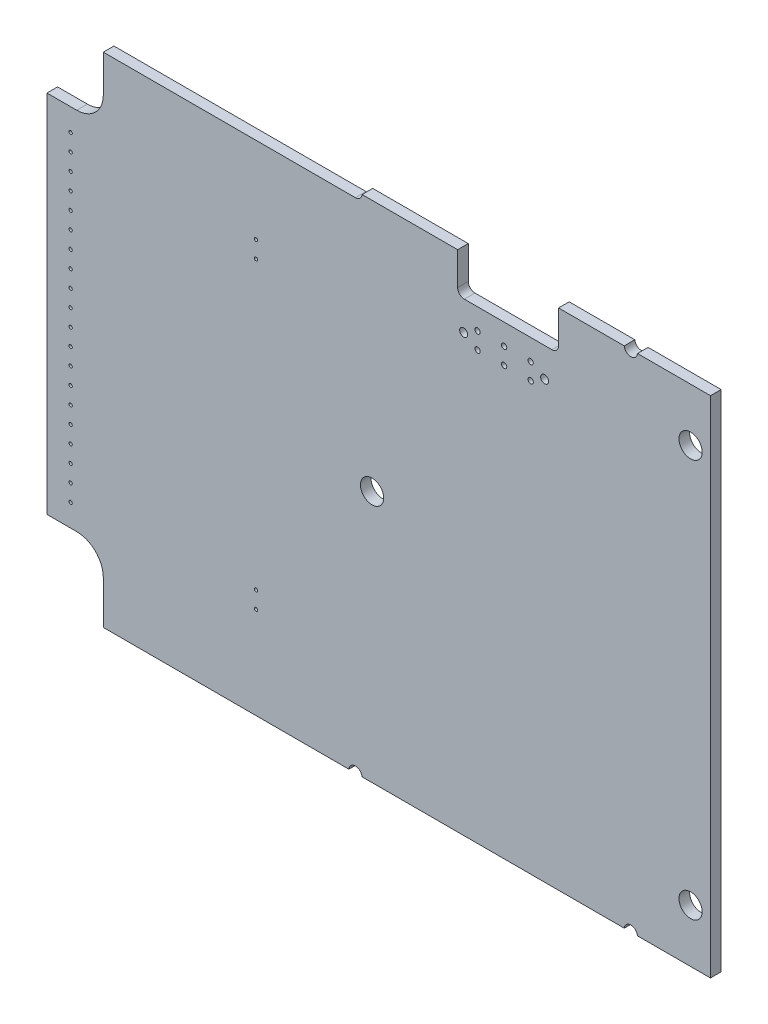
SolidWorks part; units mm, degrees
ref_plane "Płaszczyzna przednia" through (0, 0, 0) normal (0, 0, 1) x (1, 0, 0)
ref_plane "Płaszczyzna górna" through (0, 0, 0) normal (0, 1, 0) x (1, 0, 0)
ref_plane "Płaszczyzna prawa" through (0, 0, 0) normal (1, 0, 0) x (0, 0, -1)
sketch "Sketch1" plane through (0, 0, 0) normal (0, 0, 1) x (1, 0, 0)
  line L0 (293.2004, -11.8195) -> (291.7004, -11.8195) construction
  line L1 (291.7004, -11.8195) -> (291.7004, -12.7695) construction
  line L2 (308.8504, 57.7305) -> (322.0504, 57.7305)
  line L3 (293.2004, -12.7695) -> (293.2004, -11.8195) construction
  line L4 (334.7004, -11.8195) -> (333.2004, -11.8195) construction
  line L5 (333.2004, -11.8195) -> (333.2004, -12.7695) construction
  line L6 (333.2004, 63.6805) -> (333.2004, 63.2305) construction
  line L7 (334.7004, -12.7695) -> (334.7004, -11.8195) construction
  line L8 (376.2004, -11.8195) -> (374.7004, -11.8195) construction
  line L9 (374.7004, -11.8195) -> (374.7004, -12.7695) construction
  line L10 (333.2004, 63.2305) -> (333.2004, 63.1805) construction
  line L11 (376.2004, -12.7695) -> (376.2004, -11.8195) construction
  line L12 (393.4504, -5.0695) -> (393.4504, -6.5695) construction
  line L13 (393.4504, -6.5695) -> (394.4004, -6.5695) construction
  line L14 (333.2004, 63.6805) -> (332.9539, 63.6805) construction
  line L15 (394.4004, -5.0695) -> (393.4504, -5.0695) construction
  line L16 (393.4504, 57.9305) -> (393.4504, 56.4305) construction
  line L17 (393.4504, 56.4305) -> (394.4004, 56.4305) construction
  line L18 (333.2004, 63.6805) -> (323.0504, 63.6805) construction
  line L19 (394.4004, 57.9305) -> (393.4504, 57.9305) construction
  line L20 (333.2004, 63.1805) -> (334.7004, 63.1805) construction
  line L21 (334.7004, 63.1805) -> (334.7004, 64.1305) construction
  line L22 (333.2004, 64.425) -> (333.2004, 63.6805) construction
  line L23 (333.2004, 64.1305) -> (333.2004, 63.1805) construction
  line L24 (374.7004, 63.1805) -> (376.2004, 63.1805) construction
  line L25 (376.2004, 63.1805) -> (376.2004, 64.1305) construction
  line L26 (334.7004, 63.6805) -> (334.7004, 64.425) construction
  line L27 (374.7004, 64.1305) -> (374.7004, 63.1805) construction
  line L28 (291.7004, 63.1805) -> (293.2004, 63.1805) construction
  line L29 (293.2004, 63.1805) -> (293.2004, 64.1305) construction
  line L30 (291.4539, 63.6805) -> (254.4504, 63.6805) construction
  line L31 (291.7004, 64.1305) -> (291.7004, 63.1805) construction
  line L32 (376.2004, -13.3195) -> (390.9504, -13.3195) construction
  line L33 (394.9504, -9.3195) -> (394.9504, -6.5695) construction
  line L34 (394.9504, -5.0695) -> (394.9504, 56.4305) construction
  line L35 (394.9504, 57.9305) -> (394.9504, 60.6805) construction
  line L36 (390.9504, 64.6805) -> (376.2004, 64.6805) construction
  line L37 (374.7004, 64.6805) -> (334.7004, 64.6805) construction
  line L38 (307.8504, 64.6805) -> (307.8504, 65.8305) construction
  line L39 (323.0504, 64.6805) -> (323.0504, 65.8305) construction
  line L40 (333.2004, 64.6805) -> (323.0504, 64.6805) construction
  line L41 (307.8504, 64.6805) -> (293.2004, 64.6805) construction
  line L42 (291.7004, 64.6805) -> (246.9504, 64.6805) construction
  line L43 (246.9504, -8.4262) -> (246.9504, 59.7871) construction
  line L44 (334.7004, -13.3195) -> (374.7004, -13.3195) construction
  line L45 (293.2004, -13.3195) -> (333.2004, -13.3195) construction
  line L46 (246.9504, -13.3195) -> (291.7004, -13.3195) construction
  line L47 (293.2004, -11.8195) -> (291.7004, -11.8195) construction
  line L48 (291.7004, -11.8195) -> (291.7004, -13.3195) construction
  line L50 (293.2004, -13.3195) -> (293.2004, -11.8195) construction
  line L51 (334.7004, -11.8195) -> (333.2004, -11.8195) construction
  line L52 (333.2004, -11.8195) -> (333.2004, -13.3195) construction
  line L54 (334.7004, -13.3195) -> (334.7004, -11.8195) construction
  line L55 (376.2004, -11.8195) -> (374.7004, -11.8195) construction
  line L56 (374.7004, -11.8195) -> (374.7004, -13.3195) construction
  line L58 (376.2004, -13.3195) -> (376.2004, -13.0641) construction
  line L59 (393.4504, -5.0695) -> (393.4504, -6.5695) construction
  line L60 (393.4504, -6.5695) -> (394.9504, -6.5695) construction
  line L62 (394.9504, -5.0695) -> (393.4504, -5.0695) construction
  line L63 (393.4504, 57.9305) -> (393.4504, 56.4305) construction
  line L64 (393.4504, 56.4305) -> (394.6949, 56.4305) construction
  line L66 (394.9504, 57.9305) -> (393.4504, 57.9305) construction
  line L67 (333.2004, 63.1805) -> (334.7004, 63.1805) construction
  line L68 (334.7004, 63.1805) -> (334.7004, 63.6805) construction
  line L70 (333.2004, 64.6805) -> (333.2004, 64.425) construction
  line L71 (374.7004, 63.1805) -> (376.2004, 63.1805) construction
  line L72 (376.2004, 63.1805) -> (376.2004, 63.6805) construction
  line L74 (374.7004, 64.425) -> (374.7004, 63.1805) construction
  line L75 (291.7004, 63.1805) -> (293.2004, 63.1805) construction
  line L76 (293.2004, 63.1805) -> (293.2004, 64.6805) construction
  line L78 (291.7004, 64.425) -> (291.7004, 63.6805) construction
  line L79 (376.2004, -13.3195) -> (390.9504, -13.3195) construction
  line L80 (394.9504, -9.3195) -> (394.9504, -6.5695) construction
  line L81 (394.9504, -5.0695) -> (394.9504, 56.4305) construction
  line L82 (394.9504, 57.9305) -> (394.9504, 60.6805) construction
  line L83 (390.9504, 64.6805) -> (376.2004, 64.6805) construction
  line L84 (374.7004, 64.6805) -> (334.7004, 64.6805) construction
  line L85 (307.8504, 64.6805) -> (307.8504, 65.8305) construction
  line L86 (323.0504, 58.7305) -> (323.0504, 63.6805)
  line L87 (333.2004, 64.6805) -> (323.0504, 64.6805) construction
  line L88 (307.8504, 64.6805) -> (293.2004, 64.6805) construction
  line L89 (291.7004, 64.6805) -> (246.9504, 64.6805) construction
  line L90 (246.9504, -13.3195) -> (246.9504, -3.883) construction
  line L91 (334.7004, -13.3195) -> (374.7004, -13.3195) construction
  line L92 (293.2004, -13.3195) -> (333.2004, -13.3195) construction
  line L93 (246.9504, -13.3195) -> (291.7004, -13.3195) construction
  line L94 (247.9504, -12.3195) -> (247.9504, -8.942) construction
  line L95 (254.4504, -12.3195) -> (291.4539, -12.3195)
  line L96 (293.4469, -12.3195) -> (332.9539, -12.3195)
  line L97 (334.9469, -12.3195) -> (374.4539, -12.3195)
  line L98 (376.4469, -12.3195) -> (390.9504, -12.3195)
  line L99 (393.9504, -9.3195) -> (393.9504, -6.8161)
  line L100 (393.9504, -4.823) -> (393.9504, 56.4305)
  line L101 (393.9504, 58.177) -> (393.9504, 60.6805)
  line L102 (317.8504, 58.7305) -> (317.8504, 63.2305)
  line L103 (317.8504, 63.2305) -> (307.8504, 63.2305)
  line L104 (307.8504, 63.2305) -> (307.8504, 58.7305)
  line L105 (307.8504, 58.7305) -> (311.3504, 58.7305)
  line L106 (311.3504, 58.7305) -> (311.3504, 62.7305)
  line L107 (311.3504, 62.7305) -> (314.3504, 62.7305)
  line L108 (314.3504, 62.7305) -> (314.3504, 58.7305)
  line L109 (314.3504, 58.7305) -> (317.8504, 58.7305)
  line L112 (307.8504, 63.6805) -> (307.8504, 58.7305)
  line L113 (307.8504, 58.7305) -> (311.3504, 58.7305) construction
  line L114 (311.3504, 58.7305) -> (311.3504, 62.7305) construction
  line L115 (311.3504, 62.7305) -> (314.3504, 62.7305) construction
  line L116 (314.3504, 62.7305) -> (314.3504, 58.7305) construction
  line L117 (314.3504, 58.7305) -> (323.0504, 58.7305) construction
  line L118 (390.9504, 63.6805) -> (376.4469, 63.6805)
  line L119 (374.4539, 63.6805) -> (334.9469, 63.6805)
  line L120 (307.8504, 63.6805) -> (293.4469, 63.6805)
  line L121 (332.9539, 63.6805) -> (323.0504, 63.6805)
  line L122 (307.8504, 64.6805) -> (307.8504, 63.6805) construction
  line L123 (323.0504, 64.6805) -> (323.0504, 65.8305) construction
  line L124 (323.0504, 63.6805) -> (323.0504, 64.6805) construction
  line L125 (334.7004, 64.425) -> (334.7004, 64.6805) construction
  line L126 (334.9469, 63.6805) -> (334.7004, 63.6805) construction
  line L127 (374.7004, 63.6805) -> (334.7004, 63.6805) construction
  line L128 (291.7004, 63.6805) -> (291.4539, 63.6805) construction
  line L129 (291.7004, 63.6805) -> (247.9504, 63.6805) construction
  line L130 (291.7004, 64.6805) -> (291.7004, 64.425) construction
  line L131 (293.4469, 63.6805) -> (293.2004, 63.6805) construction
  line L132 (307.8504, 63.6805) -> (293.2004, 63.6805) construction
  line L133 (374.7004, 63.6805) -> (374.4539, 63.6805) construction
  line L134 (374.7004, 64.6805) -> (374.7004, 64.425) construction
  line L135 (376.2004, 63.6805) -> (376.2004, 64.425) construction
  line L136 (376.2004, 64.425) -> (376.2004, 64.6805) construction
  line L137 (376.4469, 63.6805) -> (376.2004, 63.6805) construction
  line L138 (390.9504, 63.6805) -> (376.2004, 63.6805) construction
  line L139 (394.6949, 56.4305) -> (394.9504, 56.4305) construction
  line L140 (393.9504, 57.9305) -> (393.9504, 58.177) construction
  line L141 (393.9504, 57.9305) -> (393.9504, 60.6805) construction
  line L142 (393.9504, -5.0695) -> (393.9504, -4.823) construction
  line L143 (393.9504, -5.0695) -> (393.9504, 56.4305) construction
  line L144 (393.9504, -6.8161) -> (393.9504, -6.5695) construction
  line L145 (393.9504, -9.3195) -> (393.9504, -6.5695) construction
  line L146 (376.2004, -13.0641) -> (376.2004, -12.3195) construction
  line L147 (376.2004, -12.3195) -> (376.2004, -11.8195) construction
  line L148 (376.2004, -12.3195) -> (376.4469, -12.3195) construction
  line L149 (376.2004, -12.3195) -> (390.9504, -12.3195) construction
  line L150 (293.2004, -12.3195) -> (293.4469, -12.3195) construction
  line L151 (332.9539, -12.3195) -> (333.2004, -12.3195) construction
  line L152 (293.2004, -12.3195) -> (333.2004, -12.3195) construction
  line L153 (334.7004, -12.3195) -> (334.9469, -12.3195) construction
  line L154 (334.7004, -12.3195) -> (374.7004, -12.3195) construction
  line L155 (254.4504, 57.1805) -> (254.4504, 62.7636)
  line L156 (291.4539, -12.3195) -> (291.7004, -12.3195) construction
  line L157 (247.9504, -12.3195) -> (291.7004, -12.3195) construction
  line L158 (250.4504, 53.1805) -> (245.9504, 53.1805)
  line L159 (254.4504, -5.8195) -> (254.4504, -12.3195)
  line L160 (250.4504, -1.8195) -> (245.9504, -1.8195)
  line L161 (247.9504, -1.8195) -> (247.9504, 53.1805) construction
  line L162 (247.9504, -4.1612) -> (247.9504, -2.697) construction
  line L163 (247.9504, -2.697) -> (247.9504, -1.8195) construction
  line L164 (247.9504, -12.3195) -> (247.9504, 63.6805) construction
  line L165 (247.9504, -8.942) -> (247.9504, -7.4778) construction
  line L166 (247.9504, -7.4778) -> (247.9504, -4.1612) construction
  line L167 (247.9504, -12.3195) -> (254.4504, -12.3195) construction
  line L168 (247.9504, 60.303) -> (247.9504, 63.6805) construction
  line L169 (254.4504, 63.6805) -> (247.9504, 63.6805) construction
  line L170 (247.9504, 58.8388) -> (247.9504, 60.303) construction
  line L171 (246.9504, 59.117) -> (246.9504, 64.6805) construction
  line L172 (246.9504, -13.3195) -> (246.9504, 64.6805) construction
  line L173 (246.9504, 55.244) -> (246.9504, 59.117) construction
  line L174 (247.9504, 55.5222) -> (247.9504, 58.8388) construction
  line L175 (246.9504, -3.883) -> (246.9504, 55.244) construction
  line L176 (247.9504, 54.058) -> (247.9504, 55.5222) construction
  line L177 (247.9504, 53.1805) -> (247.9504, 54.058) construction
  line L178 (249.5254, 49.8105) -> (277.4654, 49.8105) construction
  line L179 (249.5254, 49.8105) -> (249.5254, 47.2705) construction
  line L180 (374.4539, -12.3195) -> (374.7004, -12.3195) construction
  line L181 (245.4504, -8.8119) -> (245.4504, 59.8484) construction
  line L182 (245.4504, -8.8119) -> (245.4504, 59.8484) construction
  line L183 (245.9504, -1.8195) -> (245.9504, 53.1805)
  line L184 (245.9504, -8.8119) -> (245.9504, -1.8195) construction
  line L185 (245.9504, 53.1805) -> (245.9504, 59.8484) construction
  line L186 (245.9504, -8.8119) -> (245.9504, 59.8484) construction
  line L187 (292.4504, 62.7636) -> (254.4504, 62.7636)
  line L188 (254.4504, 62.7636) -> (254.4504, 63.6805) construction
  line L189 (291.7004, 63.6805) -> (291.7004, 63.2305) construction
  line L190 (291.7004, 63.2305) -> (291.7004, 63.1805) construction
  circle A0 centre (250.4504, -5.8195) radius 1.2 construction
  arc A1 (390.9504, -13.3195) -> (394.9504, -9.3195) centre (390.9504, -9.3195) ccw construction
  arc A2 (394.9504, 60.6805) -> (390.9504, 64.6805) centre (390.9504, 60.6805) ccw construction
  circle A3 centre (249.5254, 49.8105) radius 0.25 construction
  circle A4 centre (250.4504, 57.1805) radius 3 construction
  circle A5 centre (250.4504, 57.1805) radius 1.2 construction
  circle A6 centre (250.4504, -5.8195) radius 3 construction
  circle A7 centre (342.9504, -4.3195) radius 2.5 construction
  circle A8 centre (342.9504, -4.3195) radius 1 construction
  circle A9 centre (375.4504, -5.8195) radius 3 construction
  circle A10 centre (375.4504, -5.8195) radius 1.2 construction
  circle A11 centre (375.4504, 57.1805) radius 3 construction
  circle A12 centre (375.4504, 57.1805) radius 1.2 construction
  circle A13 centre (342.9504, 55.6805) radius 2.5 construction
  circle A14 centre (342.9504, 55.6805) radius 1 construction
  circle A15 centre (294.9504, 25.6805) radius 2.5 construction
  circle A16 centre (294.9504, 25.6805) radius 1 construction
  circle A17 centre (250.4504, -5.8195) radius 1.2 construction
  arc A18 (390.9504, -13.3195) -> (394.9504, -9.3195) centre (390.9504, -9.3195) ccw construction
  arc A19 (394.9504, 60.6805) -> (390.9504, 64.6805) centre (390.9504, 60.6805) ccw construction
  circle A20 centre (249.5254, 49.8105) radius 0.25 construction
  arc A21 (247.9504, 55.5222) -> (247.9504, 58.8388) centre (250.4504, 57.1805) ccw construction
  circle A22 centre (250.4504, 57.1805) radius 1.2 construction
  circle A23 centre (250.4504, -5.8195) radius 3 construction
  circle A24 centre (342.9504, -4.3195) radius 2.5 construction
  circle A25 centre (342.9504, -4.3195) radius 1 construction
  circle A26 centre (375.4504, -5.8195) radius 3 construction
  circle A27 centre (375.4504, -5.8195) radius 1.2 construction
  circle A28 centre (375.4504, 57.1805) radius 3 construction
  circle A29 centre (375.4504, 57.1805) radius 1.2 construction
  circle A30 centre (342.9504, 55.6805) radius 2.5 construction
  circle A31 centre (342.9504, 55.6805) radius 1 construction
  circle A32 centre (294.9504, 25.6805) radius 2.5 construction
  circle A33 centre (294.9504, 25.6805) radius 1 construction
  circle A34 centre (294.9504, 25.6805) radius 1.75
  circle A35 centre (342.9504, 55.6805) radius 1.75
  circle A36 centre (342.9504, -4.3195) radius 1.75
  arc A37 (250.4504, 53.1805) -> (254.4504, 57.1805) centre (250.4504, 57.1805) ccw
  arc A38 (254.4504, -5.8195) -> (250.4504, -1.8195) centre (250.4504, -5.8195) ccw
  circle A39 centre (375.4504, -5.8195) radius 4
  circle A40 centre (375.4504, 57.1805) radius 4
  arc A41 (390.9504, -12.3195) -> (393.9504, -9.3195) centre (390.9504, -9.3195) ccw
  arc A42 (393.9504, 60.6805) -> (390.9504, 63.6805) centre (390.9504, 60.6805) ccw
  arc A43 (307.8504, 58.7305) -> (308.8504, 57.7305) centre (308.8504, 58.7305) ccw
  arc A44 (322.0504, 57.7305) -> (323.0504, 58.7305) centre (322.0504, 58.7305) ccw
  circle A46 centre (333.2004, 63.1805) radius 0.05 construction
  circle A47 centre (334.7004, 63.1805) radius 0.05 construction
  arc A48 (332.9539, 63.6805) -> (334.9469, 63.6805) centre (333.9504, 63.7636) ccw
  arc A49 (333.2004, 64.425) -> (332.9539, 63.6805) centre (333.9504, 63.7636) ccw construction
  arc A50 (334.9469, 63.6805) -> (334.7004, 64.425) centre (333.9504, 63.7636) ccw construction
  arc A51 (334.7004, 64.425) -> (333.2004, 64.425) centre (333.9504, 63.7636) ccw construction
  circle A52 centre (291.7004, 63.1805) radius 0.05 construction
  circle A53 centre (293.2004, 63.1805) radius 0.05 construction
  arc A54 (293.2399, 63.1498) -> (293.4469, 63.6805) centre (292.4504, 63.7636) ccw
  arc A55 (291.7004, 64.425) -> (291.4539, 63.6805) centre (292.4504, 63.7636) ccw construction
  arc A56 (293.2004, 64.425) -> (291.7004, 64.425) centre (292.4504, 63.7636) ccw construction
  arc A57 (293.4469, 63.6805) -> (293.2004, 64.425) centre (292.4504, 63.7636) ccw construction
  circle A58 centre (374.7004, 63.1805) radius 0.05 construction
  circle A59 centre (376.2004, 63.1805) radius 0.05 construction
  arc A60 (374.4539, 63.6805) -> (376.4469, 63.6805) centre (375.4504, 63.7636) ccw
  arc A61 (374.7004, 64.425) -> (374.4539, 63.6805) centre (375.4504, 63.7636) ccw construction
  arc A62 (376.2004, 64.425) -> (374.7004, 64.425) centre (375.4504, 63.7636) ccw construction
  arc A63 (376.4469, 63.6805) -> (376.2004, 64.425) centre (375.4504, 63.7636) ccw construction
  circle A64 centre (393.4504, 57.9305) radius 0.05 construction
  circle A65 centre (393.4504, 56.4305) radius 0.05 construction
  arc A66 (393.9504, 58.177) -> (393.9504, 56.1839) centre (394.0335, 57.1805) ccw
  arc A67 (394.6949, 56.4305) -> (394.6949, 57.9305) centre (394.0335, 57.1805) ccw construction
  arc A68 (393.9504, 56.1839) -> (394.6949, 56.4305) centre (394.0335, 57.1805) ccw construction
  arc A69 (394.6949, 57.9305) -> (393.9504, 58.177) centre (394.0335, 57.1805) ccw construction
  circle A70 centre (393.4504, -6.5695) radius 0.05 construction
  circle A71 centre (393.4504, -5.0695) radius 0.05 construction
  arc A72 (393.9504, -4.823) -> (393.9504, -6.8161) centre (394.0335, -5.8195) ccw
  arc A73 (394.9504, -5.4204) -> (393.9504, -4.823) centre (394.0335, -5.8195) ccw construction
  arc A74 (393.9504, -6.8161) -> (394.9504, -6.2186) centre (394.0335, -5.8195) ccw construction
  arc A75 (394.9504, -6.2186) -> (394.9504, -5.4204) centre (394.0335, -5.8195) ccw construction
  circle A76 centre (374.7004, -11.8195) radius 0.05 construction
  circle A77 centre (376.2004, -11.8195) radius 0.05 construction
  circle A78 centre (333.2004, -11.8195) radius 0.05 construction
  circle A79 centre (334.7004, -11.8195) radius 0.05 construction
  circle A80 centre (291.7004, -11.8195) radius 0.05 construction
  circle A81 centre (293.2004, -11.8195) radius 0.05 construction
  arc A82 (376.4469, -12.3195) -> (374.4539, -12.3195) centre (375.4504, -12.4026) ccw
  arc A83 (334.9469, -12.3195) -> (332.9539, -12.3195) centre (333.9504, -12.4026) ccw
  arc A84 (293.4469, -12.3195) -> (291.4539, -12.3195) centre (292.4504, -12.4026) ccw
  arc A85 (374.4539, -12.3195) -> (374.7004, -13.0641) centre (375.4504, -12.4026) ccw construction
  arc A86 (374.7004, -13.0641) -> (376.2004, -13.0641) centre (375.4504, -12.4026) ccw construction
  arc A87 (376.2004, -13.0641) -> (376.4469, -12.3195) centre (375.4504, -12.4026) ccw construction
  arc A88 (332.9539, -12.3195) -> (333.2004, -13.0641) centre (333.9504, -12.4026) ccw construction
  arc A89 (333.2004, -13.0641) -> (334.7004, -13.0641) centre (333.9504, -12.4026) ccw construction
  arc A90 (334.7004, -13.0641) -> (334.9469, -12.3195) centre (333.9504, -12.4026) ccw construction
  arc A91 (293.2004, -13.0641) -> (293.4469, -12.3195) centre (292.4504, -12.4026) ccw construction
  arc A92 (291.7004, -13.0641) -> (293.2004, -13.0641) centre (292.4504, -12.4026) ccw construction
  arc A93 (291.4539, -12.3195) -> (291.7004, -13.0641) centre (292.4504, -12.4026) ccw construction
  arc A94 (247.9504, -2.697) -> (246.9504, -3.883) centre (250.4504, -5.8195) ccw construction
  arc A95 (250.4504, -1.8195) -> (247.9504, -2.697) centre (250.4504, -5.8195) ccw construction
  circle A96 centre (250.4504, -5.8195) radius 4 construction
  arc A97 (246.9504, -3.883) -> (246.9504, -7.756) centre (250.4504, -5.8195) ccw construction
  arc A98 (246.9504, -7.756) -> (247.9504, -8.942) centre (250.4504, -5.8195) ccw construction
  arc A99 (247.9504, -8.942) -> (254.4504, -5.8195) centre (250.4504, -5.8195) ccw construction
  arc A100 (247.9504, 60.303) -> (246.9504, 59.117) centre (250.4504, 57.1805) ccw construction
  circle A101 centre (250.4504, 57.1805) radius 4 construction
  arc A102 (246.9504, 59.117) -> (246.9504, 55.244) centre (250.4504, 57.1805) ccw construction
  arc A103 (247.9504, 58.8388) -> (247.9504, 55.5222) centre (250.4504, 57.1805) ccw construction
  circle A104 centre (250.4504, 57.1805) radius 3 construction
  arc A105 (246.9504, 55.244) -> (247.9504, 54.058) centre (250.4504, 57.1805) ccw construction
  arc A106 (247.9504, 54.058) -> (250.4504, 53.1805) centre (250.4504, 57.1805) ccw construction
  arc A107 (254.4504, 57.1805) -> (247.9504, 60.303) centre (250.4504, 57.1805) ccw construction
  circle A108 centre (277.4654, 49.8105) radius 0.25 construction
  circle A109 centre (277.4654, 47.2705) radius 0.25 construction
  arc A110 (291.4539, 63.6805) -> (291.6609, 63.1498) centre (292.4504, 63.7636) ccw construction
  arc A111 (292.4504, 62.7636) -> (293.2399, 63.1498) centre (292.4504, 63.7636) ccw
  arc A112 (291.6609, 63.1498) -> (292.4504, 62.7636) centre (292.4504, 63.7636) ccw construction
  circle A126 centre (277.4654, 4.0905) radius 0.25 construction
  circle A127 centre (277.4654, 1.5505) radius 0.25 construction
  circle A128 centre (249.5254, 47.2705) radius 0.25 construction
  circle A129 centre (249.5254, 44.7305) radius 0.25 construction
  circle A130 centre (249.5254, 42.1905) radius 0.25 construction
  circle A131 centre (249.5254, 39.6505) radius 0.25 construction
  circle A132 centre (249.5254, 37.1105) radius 0.25 construction
  circle A133 centre (249.5254, 34.5705) radius 0.25 construction
  circle A134 centre (249.5254, 32.0305) radius 0.25 construction
  circle A135 centre (249.5254, 29.4905) radius 0.25 construction
  circle A136 centre (249.5254, 26.9505) radius 0.25 construction
  circle A137 centre (249.5254, 24.4105) radius 0.25 construction
  circle A138 centre (249.5254, 21.8705) radius 0.25 construction
  circle A139 centre (249.5254, 19.3305) radius 0.25 construction
  circle A140 centre (249.5254, 16.7905) radius 0.25 construction
  circle A141 centre (249.5254, 14.2505) radius 0.25 construction
  circle A142 centre (249.5254, 11.7105) radius 0.25 construction
  circle A143 centre (249.5254, 9.1705) radius 0.25 construction
  circle A144 centre (249.5254, 6.6305) radius 0.25 construction
  circle A145 centre (249.5254, 4.0905) radius 0.25 construction
  circle A146 centre (249.5254, 1.5505) radius 0.25 construction
  circle A147 centre (277.4654, 44.7305) radius 0.25 construction
  circle A148 centre (277.4654, 42.1905) radius 0.25 construction
  circle A149 centre (277.4654, 39.6505) radius 0.25 construction
  circle A150 centre (277.4654, 37.1105) radius 0.25 construction
  circle A151 centre (277.4654, 34.5705) radius 0.25 construction
  circle A152 centre (277.4654, 32.0305) radius 0.25 construction
  circle A153 centre (277.4654, 29.4905) radius 0.25 construction
  circle A154 centre (277.4654, 26.9505) radius 0.25 construction
  circle A155 centre (277.4654, 24.4105) radius 0.25 construction
  circle A156 centre (277.4654, 21.8705) radius 0.25 construction
  circle A157 centre (277.4654, 19.3305) radius 0.25 construction
  circle A158 centre (277.4654, 16.7905) radius 0.25 construction
  circle A159 centre (277.4654, 14.2505) radius 0.25 construction
  circle A160 centre (277.4654, 11.7105) radius 0.25 construction
  circle A161 centre (277.4654, 9.1705) radius 0.25 construction
  circle A162 centre (277.4654, 6.6305) radius 0.25 construction
  point P225 (254.4504, -5.8195)
  dimension "D5" = 1
  dimension "D6" = 0.1
  dimension "D7" = 2
  dimension "D10" = 27.94
  dimension "D11" = 2.54
  dimension "D1" = 0
  dimension "D2" = 0.75
  dimension "D3" = 1
  dimension "D4" = 1
  dimension "D12" = 0.5
  dimension "D8" = 2
  dimension "D9" = 20
sketch "Sketch3" plane through (0, 0, 0) normal (0, 0, 1) x (1, 0, 0)
  line L0 (393.9504, -4.823) -> (393.9504, 56.4305) construction
  line L1 (393.9504, 58.177) -> (393.9504, 60.6805) construction
  line L2 (390.9504, 63.6805) -> (376.4469, 63.6805) construction
  line L3 (374.4539, 63.6805) -> (334.9469, 63.6805) construction
  line L4 (332.9539, 63.6805) -> (323.0504, 63.6805) construction
  line L5 (323.0504, 58.7305) -> (323.0504, 63.6805) construction
  line L6 (308.8504, 57.7305) -> (322.0504, 57.7305) construction
  line L7 (307.8504, 63.6805) -> (307.8504, 58.7305) construction
  line L8 (307.8504, 63.6805) -> (293.4469, 63.6805) construction
  line L11 (250.4504, 53.1805) -> (245.9504, 53.1805) construction
  line L12 (292.4504, 62.7636) -> (254.4504, 62.7636) construction
  line L13 (250.4504, -1.8195) -> (245.9504, -1.8195) construction
  line L14 (254.4504, -5.8195) -> (254.4504, -12.3195) construction
  line L15 (254.4504, -12.3195) -> (291.4539, -12.3195) construction
  line L16 (293.4469, -12.3195) -> (332.9539, -12.3195) construction
  line L17 (334.9469, -12.3195) -> (374.4539, -12.3195) construction
  line L18 (376.4469, -12.3195) -> (390.9504, -12.3195) construction
  line L19 (393.9504, -9.3195) -> (393.9504, -6.8161) construction
  line L20 (393.9504, -4.823) -> (393.9504, 56.1839)
  line L21 (393.9504, 58.177) -> (393.9504, 60.6805)
  line L22 (390.9504, 63.6805) -> (376.4469, 63.6805)
  line L23 (374.4539, 63.6805) -> (334.9469, 63.6805)
  line L24 (332.9539, 63.6805) -> (323.0504, 63.6805)
  line L25 (323.0504, 58.7305) -> (323.0504, 63.6805)
  line L26 (308.8504, 57.7305) -> (322.0504, 57.7305)
  line L27 (307.8504, 63.6805) -> (307.8504, 58.7305)
  line L28 (307.8504, 63.6805) -> (293.4469, 63.6805)
  line L31 (250.4504, 53.1805) -> (245.9504, 53.1805)
  line L33 (250.4504, -1.8195) -> (245.9504, -1.8195)
  line L34 (254.4504, -5.8195) -> (254.4504, -12.3195)
  line L35 (254.4504, -12.3195) -> (291.4539, -12.3195)
  line L36 (293.4469, -12.3195) -> (332.9539, -12.3195)
  line L37 (334.9469, -12.3195) -> (374.4539, -12.3195)
  line L38 (376.4469, -12.3195) -> (390.9504, -12.3195)
  line L39 (393.9504, -9.3195) -> (393.9504, -6.8161)
  line L40 (393.9504, 56.1839) -> (393.9504, 56.4305) construction
  line L41 (245.9504, -1.8195) -> (245.9504, 53.1805) construction
  line L42 (245.9504, -1.8195) -> (245.9504, 53.1805)
  line L43 (254.4504, 57.1805) -> (254.4504, 62.7636) construction
  line L44 (292.4504, 62.7636) -> (254.4504, 62.7636)
  line L45 (254.4504, 57.1805) -> (254.4504, 62.7636)
  arc A0 (393.9504, 58.177) -> (393.9504, 56.1839) centre (394.0335, 57.1805) ccw construction
  arc A1 (393.9504, 60.6805) -> (390.9504, 63.6805) centre (390.9504, 60.6805) ccw construction
  arc A2 (374.4539, 63.6805) -> (376.4469, 63.6805) centre (375.4504, 63.7636) ccw construction
  arc A3 (332.9539, 63.6805) -> (334.9469, 63.6805) centre (333.9504, 63.7636) ccw construction
  arc A4 (322.0504, 57.7305) -> (323.0504, 58.7305) centre (322.0504, 58.7305) ccw construction
  arc A5 (307.8504, 58.7305) -> (308.8504, 57.7305) centre (308.8504, 58.7305) ccw construction
  arc A6 (293.2399, 63.1498) -> (293.4469, 63.6805) centre (292.4504, 63.7636) ccw construction
  arc A7 (250.4504, 53.1805) -> (254.4504, 57.1805) centre (250.4504, 57.1805) ccw construction
  arc A8 (254.4504, -5.8195) -> (250.4504, -1.8195) centre (250.4504, -5.8195) ccw construction
  arc A9 (293.4469, -12.3195) -> (291.4539, -12.3195) centre (292.4504, -12.4026) ccw construction
  arc A10 (334.9469, -12.3195) -> (332.9539, -12.3195) centre (333.9504, -12.4026) ccw construction
  arc A11 (376.4469, -12.3195) -> (374.4539, -12.3195) centre (375.4504, -12.4026) ccw construction
  arc A12 (390.9504, -12.3195) -> (393.9504, -9.3195) centre (390.9504, -9.3195) ccw construction
  arc A13 (393.9504, -4.823) -> (393.9504, -6.8161) centre (394.0335, -5.8195) ccw construction
  arc A14 (393.9504, 58.177) -> (393.9504, 56.1839) centre (394.0335, 57.1805) ccw
  arc A15 (393.9504, 60.6805) -> (390.9504, 63.6805) centre (390.9504, 60.6805) ccw
  arc A16 (374.4539, 63.6805) -> (376.4469, 63.6805) centre (375.4504, 63.7636) ccw
  arc A17 (332.9539, 63.6805) -> (334.9469, 63.6805) centre (333.9504, 63.7636) ccw
  arc A18 (322.0504, 57.7305) -> (323.0504, 58.7305) centre (322.0504, 58.7305) ccw
  arc A19 (307.8504, 58.7305) -> (308.8504, 57.7305) centre (308.8504, 58.7305) ccw
  arc A20 (293.2399, 63.1498) -> (293.4469, 63.6805) centre (292.4504, 63.7636) ccw
  arc A21 (250.4504, 53.1805) -> (254.4504, 57.1805) centre (250.4504, 57.1805) ccw
  arc A22 (254.4504, -5.8195) -> (250.4504, -1.8195) centre (250.4504, -5.8195) ccw
  arc A23 (293.4469, -12.3195) -> (291.4539, -12.3195) centre (292.4504, -12.4026) ccw
  arc A24 (334.9469, -12.3195) -> (332.9539, -12.3195) centre (333.9504, -12.4026) ccw
  arc A25 (376.4469, -12.3195) -> (374.4539, -12.3195) centre (375.4504, -12.4026) ccw
  arc A26 (390.9504, -12.3195) -> (393.9504, -9.3195) centre (390.9504, -9.3195) ccw
  arc A27 (393.9504, -4.823) -> (393.9504, -6.8161) centre (394.0335, -5.8195) ccw
  arc A28 (292.4504, 62.7636) -> (293.2399, 63.1498) centre (292.4504, 63.7636) ccw construction
  arc A29 (292.4504, 62.7636) -> (293.2399, 63.1498) centre (292.4504, 63.7636) ccw
extrude "Boss-Extrude1" add sketch "Sketch3" along normal blind 1.6
sketch "Sketch4" plane through (0, 0, 1.6) normal (0, 0, 1) x (1, 0, 0)
  circle A0 centre (375.4504, 57.1805) radius 4 construction
  circle A1 centre (342.9504, 55.6805) radius 1.75 construction
  circle A2 centre (342.9504, -4.3195) radius 1.75 construction
  circle A3 centre (375.4504, -5.8195) radius 4 construction
  circle A4 centre (294.9504, 25.6805) radius 1.75 construction
  circle A5 centre (375.4504, 57.1805) radius 4
  circle A6 centre (342.9504, 55.6805) radius 1.75
  circle A7 centre (342.9504, -4.3195) radius 1.75
  circle A8 centre (375.4504, -5.8195) radius 4
  circle A9 centre (294.9504, 25.6805) radius 1.75
extrude "Cut-Extrude1" cut sketch "Sketch4" against normal through all
sketch "Sketch5" plane through (0, 0, 1.6) normal (0, 0, 1) x (1, 0, 0)
  line L0 (394.9504, -5.0695) -> (394.9504, 56.4305) construction
  line L1 (402.3074, 70.8974) -> (345.9504, 70.8974)
  line L2 (402.3074, 70.8974) -> (402.3074, -22.5746)
  line L3 (402.3074, -22.5746) -> (345.9504, -22.5746)
  line L4 (345.9504, 70.8974) -> (345.9504, -22.5746)
  line L5 (394.9504, -5.0695) -> (394.9504, 56.4305) construction
  line L9 (245.9504, 53.1805) -> (245.9504, -1.8195) construction
  dimension "D1" = 49
  dimension "D2" = 100
extrude "Cut-Extrude2" cut sketch "Sketch5" against normal through all
sketch "Sketch6" plane through (0, 0, 1.6) normal (0, 0, 1) x (1, 0, 0)
  circle A0 centre (249.5254, 49.8105) radius 0.25 construction
  circle A1 centre (249.5254, 49.8105) radius 0.25
  circle A2 centre (277.4654, 49.8105) radius 0.25 construction
  circle A3 centre (277.4654, 47.2705) radius 0.25 construction
  circle A4 centre (277.4654, 4.0905) radius 0.25 construction
  circle A5 centre (277.4654, 1.5505) radius 0.25 construction
  circle A6 centre (249.5254, 1.5505) radius 0.25 construction
  circle A7 centre (249.5254, 4.0905) radius 0.25 construction
  circle A8 centre (249.5254, 6.6305) radius 0.25 construction
  circle A9 centre (249.5254, 9.1705) radius 0.25 construction
  circle A10 centre (249.5254, 11.7105) radius 0.25 construction
  circle A11 centre (249.5254, 14.2505) radius 0.25 construction
  circle A12 centre (249.5254, 16.7905) radius 0.25 construction
  circle A13 centre (249.5254, 19.3305) radius 0.25 construction
  circle A14 centre (249.5254, 21.8705) radius 0.25 construction
  circle A15 centre (249.5254, 24.4105) radius 0.25 construction
  circle A16 centre (249.5254, 26.9505) radius 0.25 construction
  circle A17 centre (249.5254, 29.4905) radius 0.25 construction
  circle A18 centre (249.5254, 32.0305) radius 0.25 construction
  circle A19 centre (249.5254, 34.5705) radius 0.25 construction
  circle A20 centre (249.5254, 37.1105) radius 0.25 construction
  circle A21 centre (249.5254, 39.6505) radius 0.25 construction
  circle A22 centre (249.5254, 42.1905) radius 0.25 construction
  circle A23 centre (249.5254, 44.7305) radius 0.25 construction
  circle A24 centre (249.5254, 47.2705) radius 0.25 construction
  circle A25 centre (277.4654, 49.8105) radius 0.25
  circle A26 centre (277.4654, 47.2705) radius 0.25
  circle A27 centre (277.4654, 4.0905) radius 0.25
  circle A28 centre (277.4654, 1.5505) radius 0.25
  circle A29 centre (249.5254, 1.5505) radius 0.25
  circle A30 centre (249.5254, 4.0905) radius 0.25
  circle A31 centre (249.5254, 6.6305) radius 0.25
  circle A32 centre (249.5254, 9.1705) radius 0.25
  circle A33 centre (249.5254, 11.7105) radius 0.25
  circle A34 centre (249.5254, 14.2505) radius 0.25
  circle A35 centre (249.5254, 16.7905) radius 0.25
  circle A36 centre (249.5254, 19.3305) radius 0.25
  circle A37 centre (249.5254, 21.8705) radius 0.25
  circle A38 centre (249.5254, 24.4105) radius 0.25
  circle A39 centre (249.5254, 26.9505) radius 0.25
  circle A40 centre (249.5254, 29.4905) radius 0.25
  circle A41 centre (249.5254, 32.0305) radius 0.25
  circle A42 centre (249.5254, 34.5705) radius 0.25
  circle A43 centre (249.5254, 37.1105) radius 0.25
  circle A44 centre (249.5254, 39.6505) radius 0.25
  circle A45 centre (249.5254, 42.1905) radius 0.25
  circle A46 centre (249.5254, 44.7305) radius 0.25
  circle A47 centre (249.5254, 47.2705) radius 0.25
extrude "Cut-Extrude3" cut sketch "Sketch6" against normal through all
sketch "Sketch7" plane through (0, 0, 0) normal (0, 0, -1) x (-1, 0, 0)
  line L68 (-320.7504, 52.8336) -> (-320.7504, 53.8274) construction
  line L69 (-320.7504, 52.8336) -> (-321.1504, 52.8336) construction
  line L70 (-321.1504, 53.8274) -> (-321.1504, 52.8336) construction
  line L71 (-321.1504, 53.8274) -> (-320.7504, 53.8274) construction
  line L72 (-318.8004, 51.9305) -> (-318.9004, 51.9305) construction
  line L73 (-318.9004, 51.9305) -> (-318.9004, 52.2305) construction
  line L74 (-318.9004, 52.2305) -> (-318.8004, 52.2305) construction
  line L75 (-318.8004, 52.2305) -> (-318.8004, 51.9305) construction
  line L76 (-318.8004, 54.4305) -> (-318.9004, 54.4305) construction
  line L77 (-318.9004, 54.4305) -> (-318.9004, 54.7305) construction
  line L78 (-318.9004, 54.7305) -> (-318.8004, 54.7305) construction
  line L79 (-318.8004, 54.7305) -> (-318.8004, 54.4305) construction
  line L80 (-314.8004, 54.4305) -> (-314.9004, 54.4305) construction
  line L81 (-314.9004, 54.4305) -> (-314.9004, 54.7305) construction
  line L82 (-314.9004, 54.7305) -> (-314.8004, 54.7305) construction
  line L83 (-314.8004, 54.7305) -> (-314.8004, 54.4305) construction
  line L84 (-314.8004, 51.9305) -> (-314.9004, 51.9305) construction
  line L85 (-314.9004, 51.9305) -> (-314.9004, 52.2305) construction
  line L86 (-314.9004, 52.2305) -> (-314.8004, 52.2305) construction
  line L87 (-314.8004, 52.2305) -> (-314.8004, 51.9305) construction
  line L88 (-310.8004, 51.9305) -> (-310.9004, 51.9305) construction
  line L89 (-310.9004, 51.9305) -> (-310.9004, 52.2305) construction
  line L90 (-310.9004, 52.2305) -> (-310.8004, 52.2305) construction
  line L91 (-310.8004, 52.2305) -> (-310.8004, 51.9305) construction
  line L92 (-310.8004, 54.4305) -> (-310.9004, 54.4305) construction
  line L93 (-310.9004, 54.4305) -> (-310.9004, 54.7305) construction
  line L94 (-310.9004, 54.7305) -> (-310.8004, 54.7305) construction
  line L95 (-310.8004, 54.7305) -> (-310.8004, 54.4305) construction
  line L96 (-308.9504, 53.8274) -> (-308.5504, 53.8274) construction
  line L97 (-308.5504, 52.8336) -> (-308.5504, 53.8274) construction
  line L98 (-308.5504, 52.8336) -> (-308.9504, 52.8336) construction
  line L99 (-308.9504, 53.8274) -> (-308.9504, 52.8336) construction
  line L100 (-320.7504, 52.8336) -> (-320.7504, 53.8274) construction
  line L101 (-320.7504, 52.8336) -> (-321.1504, 52.8336) construction
  line L102 (-321.1504, 53.8274) -> (-321.1504, 52.8336) construction
  line L103 (-321.1504, 53.8274) -> (-320.7504, 53.8274) construction
  line L104 (-318.8004, 51.9305) -> (-318.9004, 51.9305) construction
  line L105 (-318.9004, 51.9305) -> (-318.9004, 52.2305) construction
  line L106 (-318.9004, 52.2305) -> (-318.8004, 52.2305) construction
  line L107 (-318.8004, 52.2305) -> (-318.8004, 51.9305) construction
  line L108 (-318.8004, 54.4305) -> (-318.9004, 54.4305) construction
  line L109 (-318.9004, 54.4305) -> (-318.9004, 54.7305) construction
  line L110 (-318.9004, 54.7305) -> (-318.8004, 54.7305) construction
  line L111 (-318.8004, 54.7305) -> (-318.8004, 54.4305) construction
  line L112 (-314.8004, 54.4305) -> (-314.9004, 54.4305) construction
  line L113 (-314.9004, 54.4305) -> (-314.9004, 54.7305) construction
  line L114 (-314.9004, 54.7305) -> (-314.8004, 54.7305) construction
  line L115 (-314.8004, 54.7305) -> (-314.8004, 54.4305) construction
  line L116 (-314.8004, 51.9305) -> (-314.9004, 51.9305) construction
  line L117 (-314.9004, 51.9305) -> (-314.9004, 52.2305) construction
  line L118 (-314.9004, 52.2305) -> (-314.8004, 52.2305) construction
  line L119 (-314.8004, 52.2305) -> (-314.8004, 51.9305) construction
  line L120 (-310.8004, 51.9305) -> (-310.9004, 51.9305) construction
  line L121 (-310.9004, 51.9305) -> (-310.9004, 52.2305) construction
  line L122 (-310.9004, 52.2305) -> (-310.8004, 52.2305) construction
  line L123 (-310.8004, 52.2305) -> (-310.8004, 51.9305) construction
  line L124 (-310.8004, 54.4305) -> (-310.9004, 54.4305) construction
  line L125 (-310.9004, 54.4305) -> (-310.9004, 54.7305) construction
  line L126 (-310.9004, 54.7305) -> (-310.8004, 54.7305) construction
  line L127 (-310.8004, 54.7305) -> (-310.8004, 54.4305) construction
  line L128 (-308.9504, 53.8274) -> (-308.5504, 53.8274) construction
  line L129 (-308.5504, 52.8336) -> (-308.5504, 53.8274) construction
  line L130 (-308.5504, 52.8336) -> (-308.9504, 52.8336) construction
  line L131 (-308.9504, 53.8274) -> (-308.9504, 52.8336) construction
  circle A8 centre (-310.8504, 54.5805) radius 0.4
  circle A9 centre (-308.7504, 53.3305) radius 0.6
  circle A10 centre (-314.8504, 54.5805) radius 0.4
  circle A11 centre (-318.8504, 54.5805) radius 0.4
  circle A12 centre (-314.8504, 52.0805) radius 0.4
  circle A13 centre (-318.8504, 52.0805) radius 0.4
  circle A14 centre (-310.8504, 52.0805) radius 0.4
  circle A15 centre (-320.9504, 53.3305) radius 0.6
  point P7 (-308.7504, 53.8274)
  point P10 (-310.9004, 54.5805)
  point P12 (-310.8504, 54.7305)
  point P20 (-308.5504, 53.3305)
  dimension "D1" = 0.8
  dimension "D2" = 1.2
extrude "Cut-Extrude4" cut sketch "Sketch7" against normal through all
